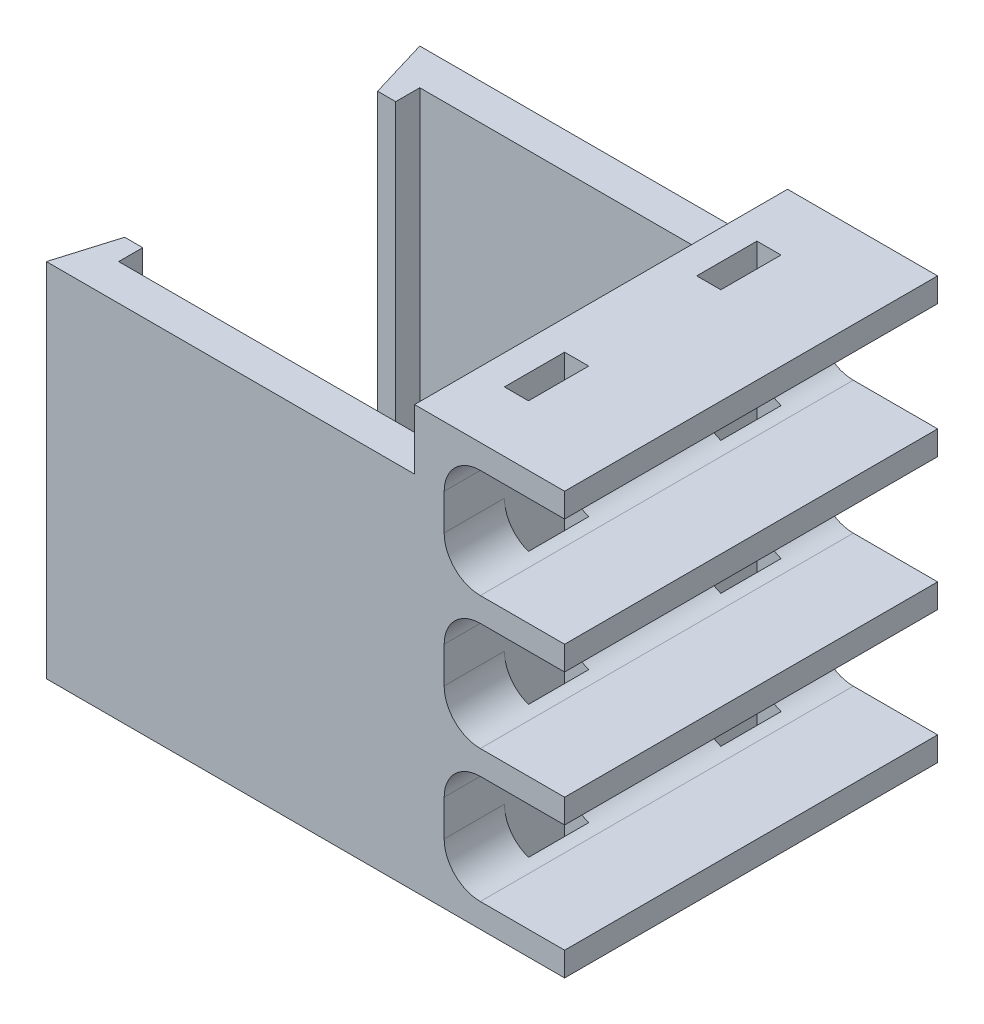
SolidWorks part; units mm, degrees
ref_plane "Спереди" through (0, 0, 0) normal (0, 0, 1) x (1, 0, 0)
ref_plane "Сверху" through (0, 0, 0) normal (0, 1, 0) x (1, 0, 0)
ref_plane "Справа" through (0, 0, 0) normal (1, 0, 0) x (0, 0, -1)
sketch "Эскиз1" plane through (0, 0, 0) normal (0, 1, 0) x (1, 0, 0)
  line L0 (-66.8258, 34.9697) -> (-66.8258, 29.9697)
  line L1 (-63.8258, 29.9697) -> (-63.8258, 31.9697)
  line L2 (-63.8258, 31.9697) -> (-38.8258, 31.9697)
  line L3 (-38.8258, 31.9697) -> (-38.8258, 6.9697)
  line L4 (-38.8258, 6.9697) -> (-63.8258, 6.9697)
  line L5 (-63.8258, 6.9697) -> (-63.8258, 8.9697)
  line L6 (-63.8258, 8.9697) -> (-66.8258, 8.9697)
  line L7 (-66.8258, 8.9697) -> (-66.8258, 3.9697)
  line L8 (-66.8258, 3.9697) -> (-22.1235, 3.9697)
  line L9 (-22.1235, 3.9697) -> (-36.579, 34.9697)
  line L10 (-36.579, 34.9697) -> (-66.8258, 34.9697)
  line L11 (-66.8258, 29.9697) -> (-63.8258, 29.9697)
  dimension "D1" = 25
  dimension "D2" = 25
  dimension "D3" = 25
  dimension "D4" = 155
  dimension "D5" = 3
  dimension "D6" = 3
  dimension "D7" = 3
  dimension "D8" = 3
  dimension "D9" = 2
  dimension "D10" = 2
extrude "Бобышка-Вытянуть1" add sketch "Эскиз1" along normal blind 30
sketch "Эскиз3" plane through (0, 0, 0) normal (0, -1, 0) x (1, 0, 0)
  line L0 (-66.8258, -3.9697) -> (-65.3258, -8.9697)
  line L1 (-63.8258, -8.9697) -> (-66.8258, -8.9697) construction
  line L2 (-65.3258, -8.9697) -> (-66.8258, -8.9697)
  line L3 (-66.8258, -8.9697) -> (-66.8258, -3.9697)
  line L4 (-66.8258, -29.9697) -> (-66.8258, -34.9697)
  line L5 (-66.8258, -34.9697) -> (-65.3258, -29.9697)
  line L6 (-66.8258, -29.9697) -> (-63.8258, -29.9697) construction
  line L7 (-65.3258, -29.9697) -> (-66.8258, -29.9697)
extrude "Вырез-Вытянуть4" cut sketch "Эскиз3" against normal through all
sketch "Эскиз7" plane through (0, 0, 0) normal (0, -1, 0) x (-1, 0, 0)
  line L1 (36.0076, 1.3029) -> (19.3993, 1.3029)
  line L2 (36.0076, 1.3029) -> (36.0076, 39.7765)
  line L3 (36.0076, 39.7765) -> (19.3993, 39.7765)
  line L4 (19.3993, 1.3029) -> (19.3993, 39.7765)
extrude "Вырез-Вытянуть14" cut sketch "Эскиз7" against normal through all
sketch "Эскиз8" plane through (0, 0, 0) normal (0, -1, 0) x (-1, 0, 0)
  line L0 (66.8258, 3.9697) -> (36.0076, 3.9697) construction
  line L1 (38.7989, 3.9697) -> (33.7989, 3.9697)
  line L2 (38.7989, 3.9697) -> (38.7989, 34.9383)
  line L3 (38.7989, 34.9383) -> (33.7989, 34.9383)
  line L4 (33.7989, 3.9697) -> (33.7989, 34.9383)
  dimension "D1" = 5
extrude "Бобышка-Вытянуть2" add sketch "Эскиз8" against normal up to surface (30 mm away) up to face at (-54.2963, 30, -20.5678)
sketch "Эскиз9" plane through (0, 0, -3.9697) normal (0, 0, 1) x (1, 0, 0)
  line L0 (-33.7989, 30) -> (-33.7989, 0) construction
  line L5 (-33.7989, 24) -> (-23.7989, 24)
  line L6 (-33.7989, 24) -> (-33.7989, 22)
  line L7 (-33.7989, 22) -> (-23.7989, 22)
  line L8 (-23.7989, 24) -> (-23.7989, 22)
  line L10 (-33.7989, 13) -> (-23.7989, 13)
  line L11 (-33.7989, 13) -> (-33.7989, 11)
  line L12 (-33.7989, 11) -> (-23.7989, 11)
  line L13 (-23.7989, 13) -> (-23.7989, 11)
  line L14 (-33.7989, 0) -> (-23.7989, 0)
  line L15 (-33.7989, 0) -> (-33.7989, 2)
  line L16 (-33.7989, 2) -> (-23.7989, 2)
  line L17 (-23.7989, 0) -> (-23.7989, 2)
  line L18 (-33.7989, 35) -> (-23.7989, 35)
  line L19 (-33.7989, 35) -> (-33.7989, 33)
  line L20 (-33.7989, 33) -> (-23.7989, 33)
  line L21 (-23.7989, 35) -> (-23.7989, 33)
  line L22 (-33.7989, 30) -> (-35.9861, 30)
  line L23 (-33.7989, 30) -> (-33.7989, 35)
  line L24 (-33.7989, 35) -> (-35.9861, 35)
  line L25 (-35.9861, 30) -> (-35.9861, 35)
  dimension "D2" = 2
  dimension "D3" = 2
  dimension "D4" = 2
  dimension "D5" = 9
  dimension "D6" = 9
  dimension "D7" = 2
  dimension "D8" = 10
  dimension "D9" = 10
  dimension "D10" = 10
  dimension "D11" = 9
sketch "Эскиз12" plane through (-33.7989, 0, 0) normal (1, 0, 0) x (0, 0, -1)
  line L0 (3.9697, 30) -> (3.9697, 35) construction
  line L1 (34.9383, 30) -> (3.9697, 30)
  line L2 (34.9383, 30) -> (34.9383, 35)
  line L3 (34.9383, 35) -> (3.9697, 35)
  line L4 (3.9697, 30) -> (3.9697, 35)
extrude "Бобышка-Вытянуть11" add sketch "Эскиз12" against normal blind 2.76
sketch "Эскиз13" plane through (0, 0, -3.9697) normal (0, 0, 1) x (1, 0, 0)
  line L1 (-33.7989, 2) -> (-23.7989, 2)
  line L2 (-33.7989, 2) -> (-33.7989, 0)
  line L3 (-33.7989, 0) -> (-23.7989, 0)
  line L4 (-23.7989, 2) -> (-23.7989, 0)
  line L5 (-33.7989, 13) -> (-23.7989, 13)
  line L6 (-33.7989, 13) -> (-33.7989, 11)
  line L7 (-33.7989, 11) -> (-23.7989, 11)
  line L8 (-23.7989, 13) -> (-23.7989, 11)
  line L9 (-33.7989, 24) -> (-23.7989, 24)
  line L10 (-33.7989, 24) -> (-33.7989, 22)
  line L11 (-33.7989, 22) -> (-23.7989, 22)
  line L12 (-23.7989, 24) -> (-23.7989, 22)
  line L13 (-33.7989, 35) -> (-23.7989, 35)
  line L14 (-33.7989, 35) -> (-33.7989, 33)
  line L15 (-33.7989, 33) -> (-23.7989, 33)
  line L16 (-23.7989, 35) -> (-23.7989, 33)
extrude "Бобышка-Вытянуть12" add sketch "Эскиз13" against normal up to surface (30.9685 mm away) up to face at (-35.6407, 21.6667, -34.9383)
sketch "Эскиз14" plane through (0, 35, 0) normal (0, 1, 0) x (1, 0, 0)
  line L0 (-36.5589, 34.9383) -> (-36.5589, 3.9697) construction
  line L1 (-33.7989, 29.9383) -> (-31.7989, 29.9383)
  line L2 (-33.7989, 29.9383) -> (-33.7989, 24.9383)
  line L3 (-33.7989, 24.9383) -> (-31.7989, 24.9383)
  line L4 (-31.7989, 29.9383) -> (-31.7989, 24.9383)
  line L5 (-33.7989, 13.9697) -> (-31.7989, 13.9697)
  line L6 (-33.7989, 13.9697) -> (-33.7989, 8.9697)
  line L7 (-33.7989, 8.9697) -> (-31.7989, 8.9697)
  line L8 (-31.7989, 13.9697) -> (-31.7989, 8.9697)
  line L9 (-36.5589, 3.9697) -> (-36.5589, 34.9383) construction
  line L10 (-36.5589, 34.9383) -> (-23.7989, 34.9383) construction
  line L11 (-33.7989, 3.9697) -> (-23.7989, 3.9697) construction
  dimension "D1" = 2
  dimension "D2" = 5
  dimension "D3" = 2
  dimension "D4" = 5
  dimension "D5" = 2.76
  dimension "D6" = 2.76
  dimension "D7" = 5
  dimension "D8" = 5
extrude "Вырез-Вытянуть15" cut sketch "Эскиз14" against normal through all
fillet "Скругление1" radius 3 6 edges at (-33.7989, 2, -6.4697) (-33.7989, 11, -6.4697) (-33.7989, 22, -6.4697) (-33.7989, 13, -6.4697) (-33.7989, 24, -6.4697) (-33.7989, 33, -6.4697)
sketch "Эскиз15" plane through (0, 0, -3.9697) normal (0, 0, 1) x (1, 0, 0)
  line L0 (-36.5589, 35) -> (-23.7989, 35) construction
  line L1 (-36.5589, 30) -> (-36.2589, 30)
  line L2 (-36.5589, 30) -> (-36.5589, 35)
  line L3 (-36.5589, 35) -> (-36.2589, 35)
  line L4 (-36.2589, 30) -> (-36.2589, 35)
  dimension "D1" = 0.3
extrude "Вырез-Вытянуть17" cut sketch "Эскиз15" against normal through all
